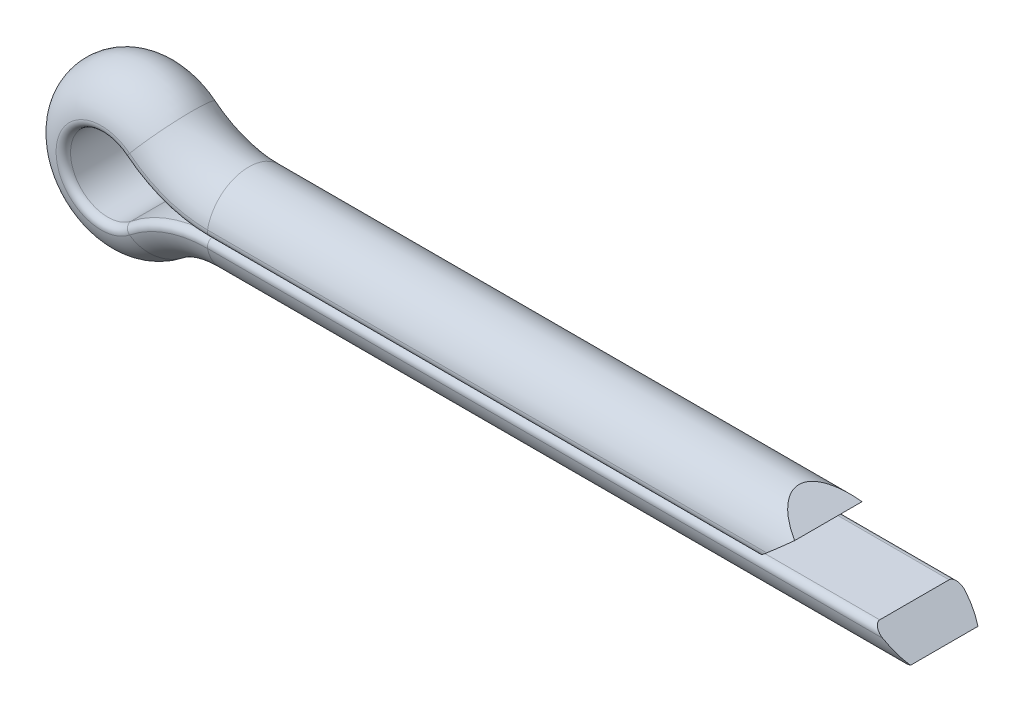
SolidWorks part; units mm, degrees
ref_plane "Front Plane" through (0, 0, 0) normal (0, 0, 1) x (1, 0, 0)
ref_plane "Top Plane" through (0, 0, 0) normal (0, 1, 0) x (1, 0, 0)
ref_plane "Right Plane" through (0, 0, 0) normal (1, 0, 0) x (0, 0, -1)
sketch "PathSke" plane through (0, 0, 0) normal (0, 0, 1) x (1, 0, 0)
  line L0 (0, 0) -> (38.8652, 0) construction
  line L1 (0, 0) -> (0, 12.2501) construction
  line L2 (3.665, 0) -> (3.665, 12.2501) construction
  line L3 (3.665, 1.45) -> (23.665, 1.45)
  line L4 (3.665, -1.45) -> (27.665, -1.45)
  line L5 (0, 0) -> (-2.735, 0) construction
  arc A0 (1.7079, 2.1362) -> (1.7079, -2.1362) centre (0, 0) ccw
  arc A1 (3.665, 1.45) -> (1.7079, 2.1362) centre (3.665, 4.584) cw
  arc A2 (3.665, -1.45) -> (1.7079, -2.1362) centre (3.665, -4.584) ccw
  dimension "Diameter" = 2.9
  dimension "Head_height" = 6.4
ref_plane "SectionPlane" through (23.665, 1.45, 0) normal (1, 0, 0) x (0, 0, -1)
sketch "SectionSke" plane through (23.665, 1.45, 0) normal (1, 0, 0) x (0, 0, -1)
  line L0 (0, -1.45) -> (0, 8.6928) construction
  line L1 (0, -1.45) -> (0, 10.8001) construction
  line L2 (-1.45, -1.45) -> (1.45, -1.45) construction
  line L3 (-1.1977, -1.448) -> (1.1977, -1.448)
  arc A0 (1.4235, -1.1743) -> (-1.4235, -1.1743) centre (0, -1.45) ccw
  arc A1 (-1.1977, -1.448) -> (-1.4235, -1.1743) centre (-1.1977, -1.218) cw
  arc A2 (1.4235, -1.1743) -> (1.1977, -1.448) centre (1.1977, -1.218) cw
  dimension "D1" = 0.002
  dimension "Diameter" = 2.9
sweep "BaseBody" add profiles "SectionSke" path "PathSke"
sketch "ConeCutSke" plane through (0, 0, 0) normal (0, 0, 1) x (1, 0, 0)
  line L0 (0, 0) -> (34.6884, 0) construction
  line L1 (22.6339, 1.46) -> (27.675, 1.46)
  line L2 (27.675, 1.46) -> (27.675, -1.46)
  line L3 (23.665, 1.45) -> (3.665, 1.45) construction
  line L4 (22.6339, 1.46) -> (23.665, 0.8629)
  line L5 (23.665, 0.2757) -> (23.665, 1.45) construction
  line L6 (23.665, 0.8629) -> (22.6339, 0)
  line L7 (22.6339, 0) -> (26.6339, 0)
  line L8 (26.6339, 0) -> (27.665, -0.8629)
  line L9 (27.665, -1.45) -> (27.665, -0.2757) construction
  line L10 (27.665, -0.8629) -> (26.6339, -1.46)
  line L11 (26.6339, -1.46) -> (27.675, -1.46)
  point P19 (27.675, 0)
  dimension "D1" = 0.01
  dimension "D2" = 70
  dimension "D3" = 70
  dimension "D4" = 0.01
extrude "ConeCut" cut sketch "ConeCutSke" against normal through all and the other way through all
equation "\"Diameter@SectionSke\" = \"Diameter@PathSke\""
